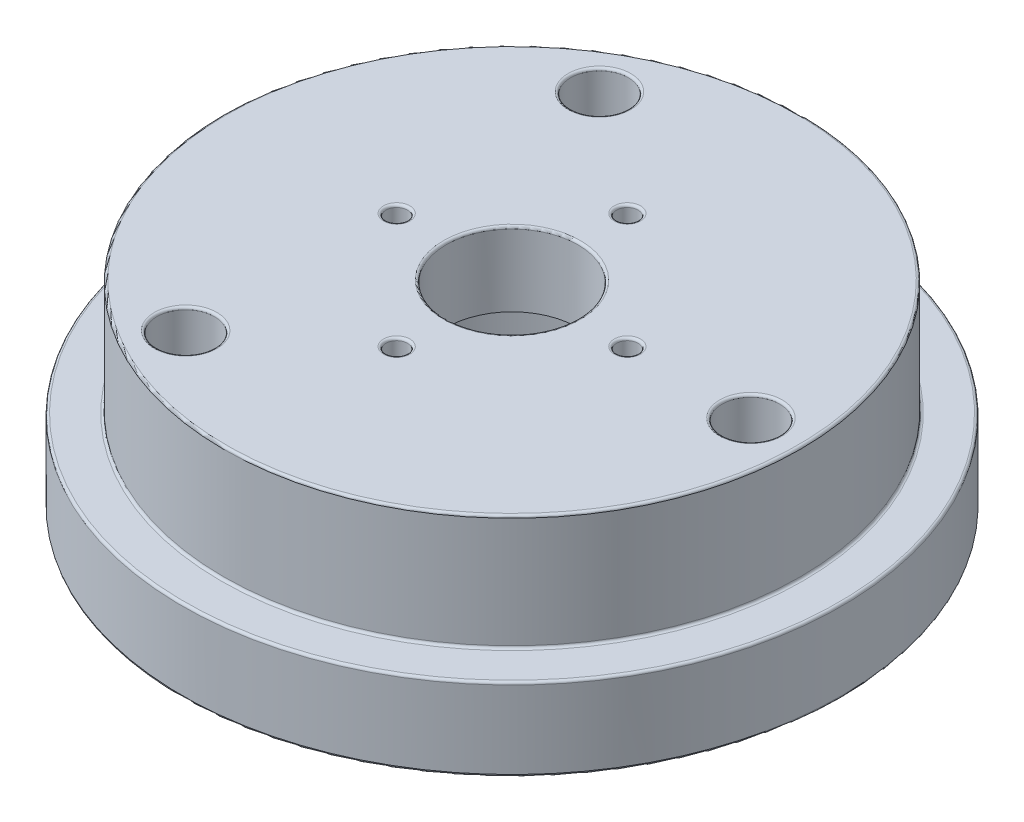
SolidWorks part; units mm, degrees
ref_plane "Front Plane" through (0, 0, 0) normal (0, 0, 1) x (1, 0, 0)
ref_plane "Top Plane" through (0, 0, 0) normal (0, 1, 0) x (1, 0, 0)
ref_plane "Right Plane" through (0, 0, 0) normal (1, 0, 0) x (0, 0, -1)
sketch "Sketch2" plane through (0, 0, 0) normal (0, 0, 1) x (1, 0, 0)
  line L0 (0, 0) -> (-20, 0)
  line L1 (-20, 0) -> (-20, 5)
  line L2 (-20, 5) -> (-17.5, 5)
  line L3 (-17.5, 5) -> (-17.5, 12)
  line L4 (-17.5, 12) -> (0, 12)
  line L5 (0, 12) -> (0, 0)
  dimension "D1" = 20
  dimension "D2" = 5
  dimension "D3" = 12
  dimension "D4" = 17.5
revolve "Revolve1" add sketch "Sketch2" angle 360 about L5
sketch "Sketch3" plane through (0, 0, 0) normal (0, -1, 0) x (1, 0, 0)
  circle A0 centre (0, 0) radius 10
  circle A1 centre (14.5, 0) radius 1.75
  circle A2 centre (-7.25, -12.5574) radius 1.75
  circle A3 centre (-7.25, 12.5574) radius 1.75
  circle A4 centre (0, 0) radius 20 construction
  circle A5 centre (0, 0) radius 4
  circle A6 centre (7, 0) radius 0.65
  circle A7 centre (0, -7) radius 0.65
  circle A8 centre (-7, 0) radius 0.65
  circle A9 centre (0, 7) radius 0.65
  point P12 (0, 0)
  point P24 (0, 0)
  dimension "D1" = 20
  dimension "D2" = 3.5
  dimension "D6" = 8
  dimension "D7" = 1.3
  dimension "D3" = 14.5
  dimension "D5" = 14.5
  dimension "D8" = 7
  dimension "D10" = 7
  dimension "D4" = 3
  dimension "D9" = 4
extrude "Cut-Extrude1" cut sketch "Sketch3" against normal through all contours A3 | A7 | A9 | A6 | A8 | A1 | A2 | A5 region at (-7.25, 0, 12.5574) region at (0, 0, -7) region at (0, 0, 7)
extrude "Cut-Extrude2" cut sketch "Sketch3<3>" against normal blind 7.5
sketch "Sketch3<3>" plane through (0, 0, 0) normal (0, -1, 0) x (1, 0, 0) same geometry as "Sketch3"
fillet "Fillet1" radius 0.15 16 edges at (-20, 0, 0) (-5.5, 0, -12.5574) (16.25, 0, 0) (-5.5, 0, 12.5574) (10, 0, 0) (-17.5, 5, 0) (-20, 5, 0) (-17.5, 12, 0) (-6.35, 12, 0) (7.65, 12, 0) (0.65, 12, 7) (0.65, 12, -7) (4, 12, 0) (-5.5, 12, -12.5574) (16.25, 12, 0) (-5.5, 12, 12.5574)
